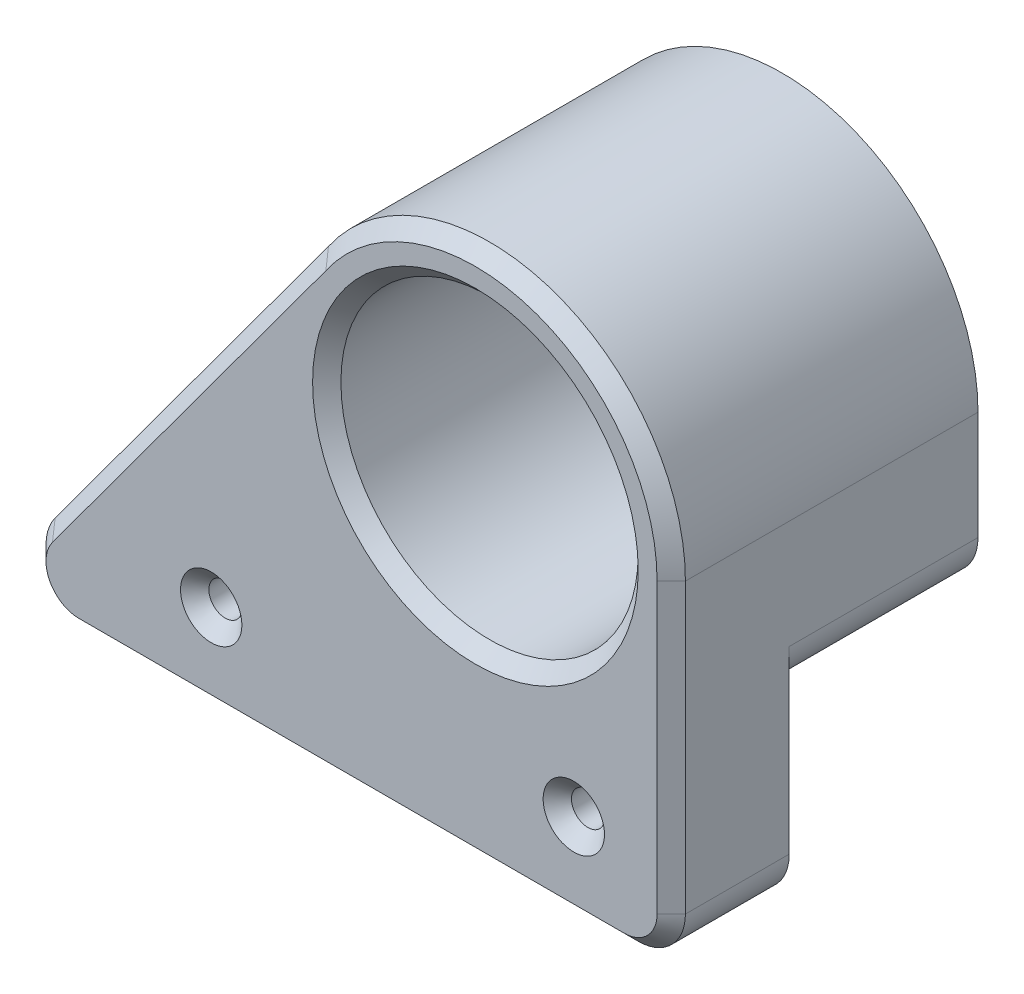
SolidWorks part; units mm, degrees
ref_plane "Front Plane" through (0, 0, 0) normal (0, 0, 1) x (1, 0, 0)
ref_plane "Top Plane" through (0, 0, 0) normal (0, 1, 0) x (1, 0, 0)
ref_plane "Right Plane" through (0, 0, 0) normal (1, 0, 0) x (0, 0, -1)
sketch "Sketch1" plane through (0, 0, 0) normal (0, 0, 1) x (1, 0, 0)
  line L0 (296.5, 0) -> (300, 0)
  line L3 (296.5, 8) -> (300, 8)
  line L4 (296.5, 41) -> (296.5, -69)
  line L5 (150, -99) -> (266.5, -99)
  line L6 (220.8686, 64.6072) -> (129.8574, -59.1921)
  circle A1 centre (150, -74) radius 5.5
  circle A2 centre (255, 41) radius 31.5
  arc A3 (129.8574, -59.1921) -> (150, -99) centre (150, -74) ccw
  arc A4 (296.5, 41) -> (220.8686, 64.6072) centre (255, 41) ccw
  circle A6 centre (255, 41) radius 41.5 construction
  arc A7 (296.5, -69) -> (266.5, -99) centre (266.5, -69) cw
  circle A9 centre (150, -74) radius 25 construction
  point P3 (210, 0)
  point P5 (210, 8)
  point P13 (294.6866, 53.1334)
  point P23 (175, -74)
  dimension "D1" = 30
  dimension "D3" = 10
extrude "Boss-Extrude1" add sketch "Sketch1" along normal blind 25 contours A7 L4 A4 L6 A3 L5 A2 A1
sketch "Sketch2" plane through (0, 0, 0) normal (0, 0, -1) x (-1, 0, 0)
  line L4 (-296.5, 41) -> (-296.5, -69) construction
  line L5 (-300, 8) -> (300, 8)
  line L6 (-296.5, 8) -> (-179.2537, 8)
  line L7 (-220.8686, 64.6072) -> (-129.8574, -59.1921) construction
  line L8 (-296.5, 41) -> (-296.5, 8)
  line L9 (-220.8686, 64.6072) -> (-179.2537, 8)
  circle A3 centre (-255, 41) radius 31.5 construction
  arc A4 (-220.8686, 64.6072) -> (-296.5, 41) centre (-255, 41) ccw construction
  circle A5 centre (-255, 41) radius 31.5
  arc A6 (-220.8686, 64.6072) -> (-296.5, 41) centre (-255, 41) ccw
  dimension "D1" = 8
extrude "Boss-Extrude2" add sketch "Sketch2" along normal blind 40
fillet "Fillet1" radius 10 2 edges at (296.5, 8, -20) (179.2537, 8, -20)
sketch "Sketch3" plane through (0, 0, 0) normal (0, 0, -1) x (-1, 0, 0)
  line L1 (-296.5, 18) -> (-296.5, -69) construction
  line L2 (-286.5, -30.1) -> (-199.0167, -30.1)
  line L3 (-286.5, -30.1) -> (-199.0167, -30.1)
  line L4 (-150, -99) -> (-266.5, -99) construction
  line L5 (-190.9597, 23.9232) -> (-129.8574, -59.1921) construction
  line L6 (-296.5, -30.1) -> (-296.5, -69)
  line L7 (-150, -99) -> (-266.5, -99)
  line L8 (-151.2445, -30.1) -> (-129.8574, -59.1921)
  line L9 (-286.5, -30.1) -> (-296.5, -30.1)
  line L10 (-199.0167, -30.1) -> (-151.2445, -30.1)
  arc A0 (-296.5, -69) -> (-266.5, -99) centre (-266.5, -69) ccw construction
  arc A1 (-150, -99) -> (-129.8574, -59.1921) centre (-150, -74) ccw construction
  arc A2 (-296.5, -69) -> (-266.5, -99) centre (-266.5, -69) ccw
  arc A3 (-150, -99) -> (-129.8574, -59.1921) centre (-150, -74) ccw
  dimension "D1" = 38.1
extrude "Cut-Extrude1" cut sketch "Sketch3" against normal through all
fillet "Fillet2" radius 10 2 edges at (296.5, -30.1, 12.5) (151.2445, -30.1, 12.5)
sketch "Sketch4" plane through (0, 0, 0) normal (0, 0, -1) x (-1, 0, 0)
  line L2 (-286.5, -11.05) -> (-199.0167, -11.05)
  line L3 (-286.5, -11.05) -> (-199.0167, -11.05)
  circle A0 centre (-199.0167, -11.05) radius 3.5
  circle A1 centre (-275.8522, -11.05) radius 3.5
  dimension "D1" = 19.05
extrude "Cut-Extrude2" cut sketch "Sketch4" against normal through all contours A0 | A1
chamfer "Chamfer1" distance 3 angle 45 9 edges at (286.5, 41, 25) (191.9095, 25.2152, 25) (267.3652, 80.615, 25) (296.5, 10.45, 25) (162.0847, -24.6149, 25) (293.5711, -27.1711, 25) (228.7537, -30.1, 25) (272.3522, -11.05, 25) (195.5167, -11.05, 25)
